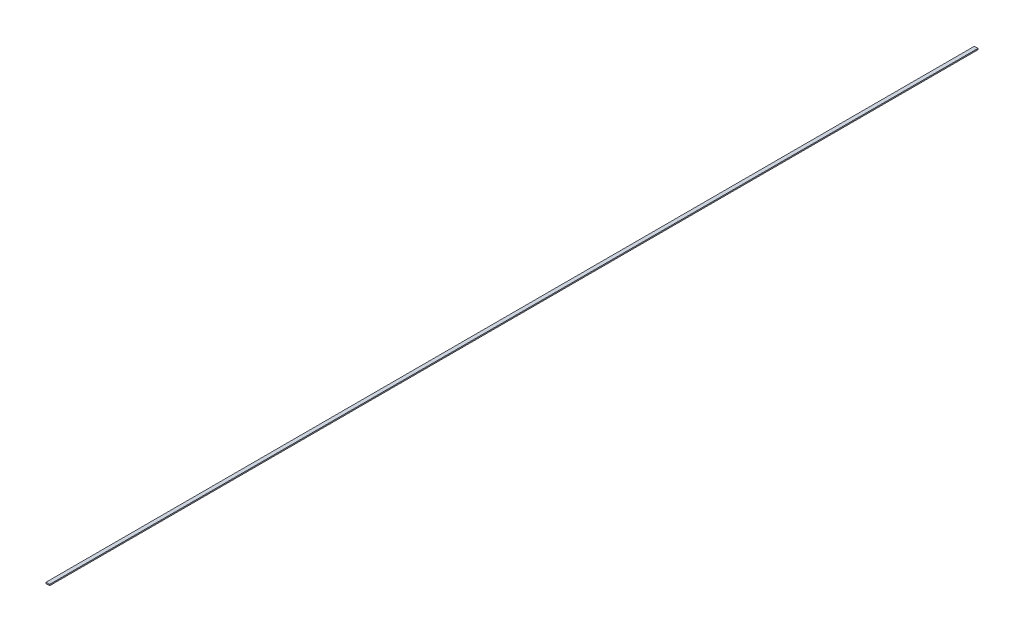
SolidWorks part; units mm, degrees
material "Thornel Mat VMA"
ref_plane "前视基准面" through (0, 0, 0) normal (0, 0, 1) x (1, 0, 0)
ref_plane "上视基准面" through (0, 0, 0) normal (0, 1, 0) x (1, 0, 0)
ref_plane "右视基准面" through (0, 0, 0) normal (1, 0, 0) x (0, 0, -1)
other "Configuration Table"
sketch "草图1" plane through (0, 0, 0) normal (0, 0, 1) x (1, 0, 0)
  line L1 (151.8745, -5.1918) -> (148.8745, -5.1918)
  line L2 (151.8745, -5.1918) -> (151.8745, -6.1918)
  line L3 (151.8745, -6.1918) -> (148.8745, -6.1918)
  line L4 (148.8745, -5.1918) -> (148.8745, -6.1918)
extrude "凸台-拉伸1" add sketch "草图1" along normal blind 759.5
